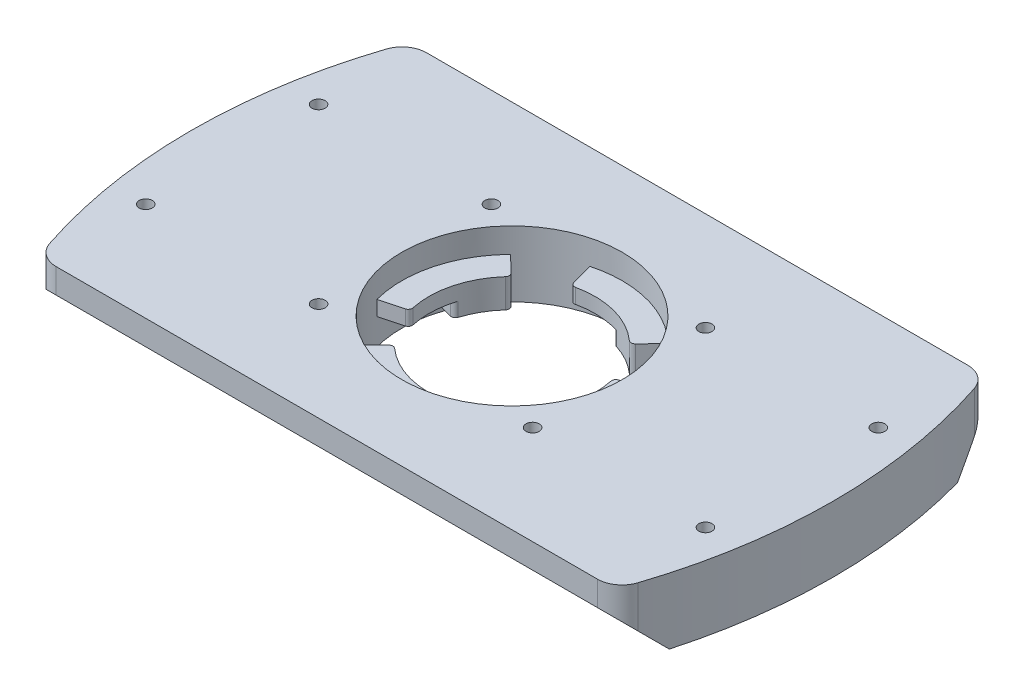
SolidWorks part; units mm, degrees
material "ABS"
ref_plane "正面" through (0, 0, 0) normal (0, 0, 1) x (1, 0, 0)
ref_plane "平面" through (0, 0, 0) normal (0, 1, 0) x (1, 0, 0)
ref_plane "右側面" through (0, 0, 0) normal (1, 0, 0) x (0, 0, -1)
sketch "ｽｹｯﾁ2" plane through (0, 0, 0) normal (0, 1, 0) x (1, 0, 0)
  line L0 (-35, 22.5) -> (-35, -22.5) construction
  line L1 (26.2812, 0) -> (0, 0) construction
  line L2 (0, 0) -> (-26.2812, 0) construction
  line L3 (-35, 22.5) -> (35, 22.5)
  line L4 (-35, -22.5) -> (35, -22.5)
  line L5 (35, 22.5) -> (35, -22.5) construction
  line L6 (-39, 0) -> (39, 0) construction
  arc A0 (-35, 22.5) -> (-35, -22.5) centre (26.2812, 0) ccw
  arc A1 (35, 22.5) -> (35, -22.5) centre (-26.2812, 0) cw
  dimension "D1" = 45
  dimension "D2" = 78
  dimension "D3" = 70
extrude "ﾎﾞｽ - 押し出し1" add sketch "ｽｹｯﾁ2" along normal mid plane 8
sketch "ｽｹｯﾁ9" plane through (0, -4, 0) normal (0, -1, 0) x (1, 0, 0)
  circle A0 centre (0, 0) radius 13.4
  dimension "D1" = 26.8
extrude "ｶｯﾄ - 押し出し1" cut sketch "ｽｹｯﾁ9" against normal through all
fillet "ﾌｨﾚｯﾄ4" radius 3 4 edges at (-35, 0, -22.5) (35, 0, -22.5) (35, 0, 22.5) (-35, 0, 22.5)
chamfer "面取り3" distance 5 angle 45 2 edges at (0, -4, -22.5) (0, -4, 22.5) tangent propagation no
sketch "ｽｹｯﾁ10" plane through (0, -4, 0) normal (0, -1, 0) x (1, 0, 0)
  circle A0 centre (-23.5, 0) radius 3.9
  dimension "D1" = 7.8
  dimension "D2" = 23.5
  dimension "D3" = 0
extrude "ﾎﾞｽ - 押し出し8" add sketch "ｽｹｯﾁ10" along normal blind 1
hole_wizard "M2 ねじ穴1" positions "ｽｹｯﾁ11" profile "ｽｹｯﾁ12" tap size "M2" standard "ISO"
sketch "ｽｹｯﾁ11" plane through (0, -4, 0) normal (0, -1, 0) x (-1, 0, 0)
  line L0 (13, -10.5) -> (23.5, 0) construction
  line L1 (23.5, 0) -> (9.5047, 0) construction
  point P0 (13, -10.5)
  dimension "D1" = 45
  dimension "D2" = 10.5
sketch "ｽｹｯﾁ12" plane through (-13, -4, 10.5) normal (1, 0, 0) x (0, 0, -1)
  line L0 (0, 0) -> (0, 10.4807)
  line L1 (0, 10.4807) -> (0.8, 10)
  line L2 (0.8, 10) -> (0.8, 0)
  line L5 (0.8, 0) -> (0, 0)
  line L10 (0, 10.4807) -> (-0.8, 10) construction
  line L11 (0, -6.35) -> (0, 107.95) construction
  dimension "ねじ下穴ﾄﾞﾘﾙ直径" = 1.6
  dimension "ねじ下穴ﾄﾞﾘﾙの深さ" = 10
  dimension "ﾄﾞﾘﾙ角度" = 118
cosmetic thread "穴のねじ山1" parameters "D1"=4, "D2"=2
pattern_circular "円形ﾊﾟﾀｰﾝ4" count 4 over 360 about axis through (-23.5, -5, 0) along (0, 1, 0) of "M2 ねじ穴1"
cosmetic thread "穴のねじ山2" parameters "D1"=4, "D2"=2
cosmetic thread "穴のねじ山3" parameters "D1"=4, "D2"=2
cosmetic thread "穴のねじ山4" parameters "D1"=4, "D2"=2
mirror "ﾐﾗｰ3" about plane through (0, 0, 0) normal (1, 0, 0) of "円形ﾊﾟﾀｰﾝ4", "M2 ねじ穴1", "ﾎﾞｽ - 押し出し8"
ref_plane "平面1" through (0, 1, 0) normal (0, 1, 0) x (1, 0, 0)
sketch "ｽｹｯﾁ13" plane through (0, 1, 0) normal (0, 1, 0) x (1, 0, 0)
  line L0 (-9.3922, -9.5576) -> (-7.0792, -7.2038)
  line L1 (-7.0792, -7.2038) -> (0, 0) construction
  line L2 (0, 0) -> (2.6141, -9.7559) construction
  line L3 (2.6141, -9.7559) -> (3.4682, -12.9434)
  line L4 (0, 0) -> (13.4, 0) construction
  arc A0 (-9.3922, -9.5576) -> (3.4682, -12.9434) centre (0, 0) ccw
  circle A1 centre (0, 0) radius 13.4 construction
  arc A2 (-7.0792, -7.2038) -> (2.6141, -9.7559) centre (0, 0) ccw
  dimension "D3" = 10.1
  dimension "D1" = 75
  dimension "D2" = 59.5
extrude "ﾎﾞｽ - 押し出し9" add sketch "ｽｹｯﾁ13" against normal blind 3.5
sketch "ｽｹｯﾁ14" plane through (0, -2.5, 0) normal (0, -1, 0) x (1, 0, 0)
  line L0 (0, 0) -> (3.4682, 12.9434)
  line L1 (-3.4682, 12.9434) -> (0, 0)
  arc A0 (3.4682, 12.9434) -> (-3.4682, 12.9434) centre (0, 0) ccw
  dimension "D1" = 30
extrude "ｶｯﾄ - 押し出し2" cut sketch "ｽｹｯﾁ14" against normal blind 1.7
fillet "ﾌｨﾚｯﾄ5" radius 0.5 3 edges at (2.6141, 0.1, 9.7559) (-2.6141, -1.65, 9.7559) (-7.0792, -0.75, 7.2038)
pattern_circular "円形ﾊﾟﾀｰﾝ5" count 4 over 360 about axis through (0, 4, 0) along (0, -1, 0) of "ﾎﾞｽ - 押し出し9", "ﾌｨﾚｯﾄ5", "ｶｯﾄ - 押し出し2"
